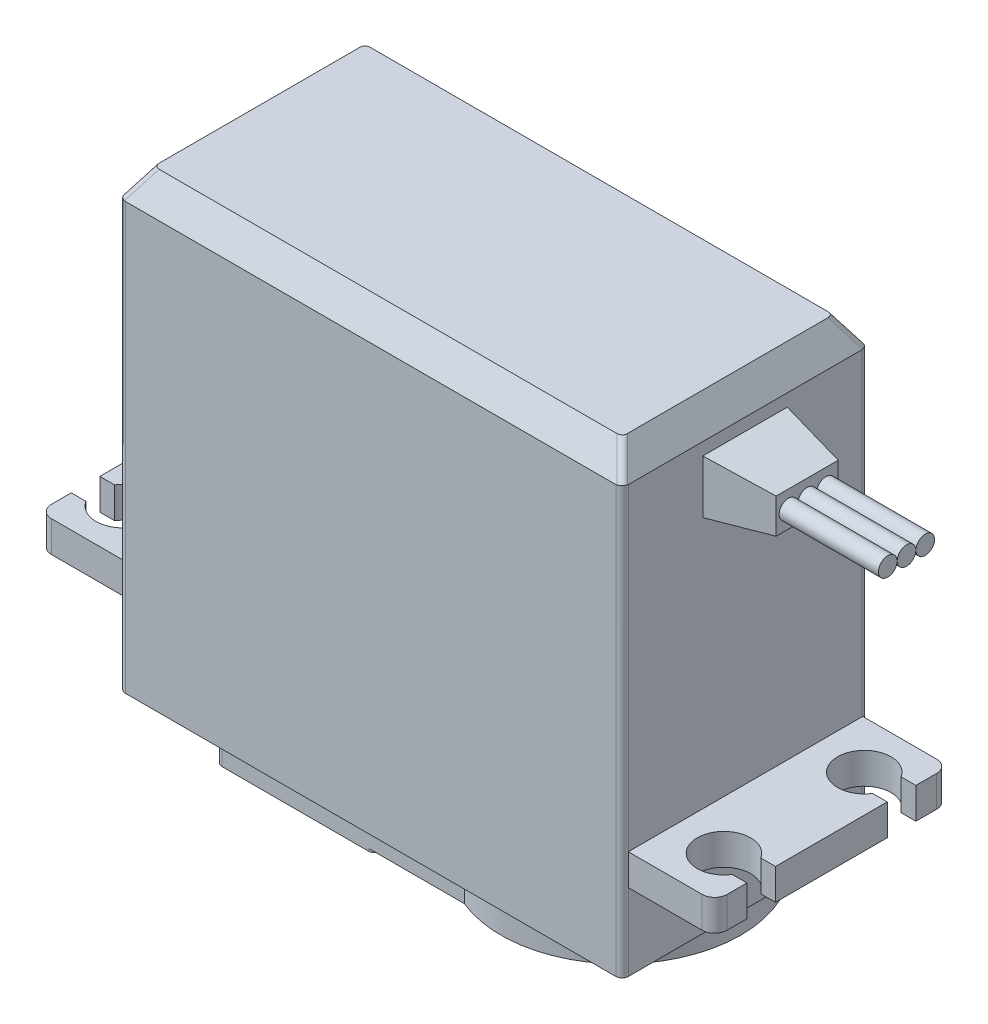
SolidWorks part; units mm, degrees
ref_plane "Front" through (0, 0, 0) normal (0, 0, 1) x (1, 0, 0)
ref_plane "Top" through (0, 0, 0) normal (0, 1, 0) x (1, 0, 0)
ref_plane "Right" through (0, 0, 0) normal (1, 0, 0) x (0, 0, -1)
sketch "Эскиз1" plane through (0, 0, 0) normal (0, 1, 0) x (1, 0, 0)
  line L1 (20.25, -9.9) -> (-20.25, -9.9)
  line L2 (20.25, -9.9) -> (20.25, 9.9)
  line L3 (20.25, 9.9) -> (-20.25, 9.9)
  line L4 (-20.25, -9.9) -> (-20.25, 9.9)
  line L5 (0, 9.9) -> (0, -9.9) construction
  line L6 (20.25, 0) -> (-20.25, 0) construction
  point P0 (0, 0)
  dimension "D1" = 19.8
  dimension "D2" = 40.5
extrude "Body" add sketch "Эскиз1" along normal blind 36.5
chamfer "Фаска1" distance 2.2 distance2 1.4 4 edges at (-20.25, 36.5, 0) (0, 36.5, -9.9) (20.25, 36.5, 0) (0, 36.5, 9.9) first distance on face at (-20.25, 18.25, 0) first distance on face at (0, 18.25, -9.9) first distance on face at (20.25, 18.25, 0) first distance on face at (0, 18.25, 9.9)
fillet "Скругление1" radius 0.5 8 edges at (-20.25, 17.15, -9.9) (-19.55, 35.4, -9.2) (19.55, 35.4, -9.2) (20.25, 17.15, -9.9) (19.55, 35.4, 9.2) (-19.55, 35.4, 9.2) (20.25, 17.15, 9.9) (-20.25, 17.15, 9.9)
ref_plane "Плоскость1" through (0, 6.2, 0) normal (0, -1, 0) x (-1, 0, 0)
sketch "Эскиз2" plane through (0, 6.2, 0) normal (0, -1, 0) x (-1, 0, 0)
  line L0 (-19.75, 9.9) -> (19.75, 9.9) construction
  line L1 (-26.2, 9.4728) -> (26.2, 9.4728)
  line L2 (27.2, -8.4) -> (27.2, -6.8)
  line L3 (-26.2, -9.4) -> (26.2, -9.4)
  line L4 (-27.2, -8.4) -> (-27.2, -6.8)
  line L5 (0, 9.9) -> (0, -9.9) construction
  line L6 (27.2, 0) -> (-27.2, 0) construction
  line L7 (-24.2, 5.65) -> (-27.2, 5.65) construction
  line L8 (-26.0166, 6.8) -> (-27.2, 6.8)
  line L9 (-26.0166, 4.5) -> (-27.2, 4.5)
  line L10 (-27.2, 6.8) -> (-27.2, 8.4728)
  line L11 (-26.0166, -4.5) -> (-27.2, -4.5)
  line L12 (-26.0166, -6.8) -> (-27.2, -6.8)
  line L13 (26.0166, -6.8) -> (27.2, -6.8)
  line L14 (26.0166, -4.5) -> (27.2, -4.5)
  line L15 (26.0166, 4.5) -> (27.2, 4.5)
  line L16 (26.0166, 6.8) -> (27.2, 6.8)
  line L17 (27.2, 6.8) -> (27.2, 8.4728)
  line L18 (27.2, -4.5) -> (27.2, 4.5)
  line L19 (-27.2, -4.5) -> (-27.2, 4.5)
  arc A0 (27.2, -8.4) -> (26.2, -9.4) centre (26.2, -8.4) cw
  arc A1 (26.2, 9.4728) -> (27.2, 8.4728) centre (26.2, 8.4728) cw
  arc A2 (-27.2, -8.4) -> (-26.2, -9.4) centre (-26.2, -8.4) ccw
  arc A3 (-27.2, 8.4728) -> (-26.2, 9.4728) centre (-26.2, 8.4728) cw
  arc A4 (-26.0166, 4.5) -> (-26.0166, 6.8) centre (-24.2, 5.65) ccw
  arc A5 (-26.0166, -4.5) -> (-26.0166, -6.8) centre (-24.2, -5.65) cw
  arc A6 (26.0166, -4.5) -> (26.0166, -6.8) centre (24.2, -5.65) ccw
  arc A7 (26.0166, 4.5) -> (26.0166, 6.8) centre (24.2, 5.65) cw
  point P0 (0, 0)
  point P10 (27.2, 9.9)
  point P16 (-27.2, 9.9)
  dimension "D2" = 1
  dimension "D4" = 4.3
  dimension "D1" = 54.4
  dimension "D5" = 3
  dimension "D6" = 1.15
extrude "Mount" add sketch "Эскиз2" against normal blind 2.5 contours L15 A7 L16 L17 A1 L1 A3 L10 L8 A4 L9 L4 L11 A5 L12 A2 L3 A0 L2 L13 A6 L14 L18 region at (0, 6.2, -0.039)
sketch "Эскиз3" plane through (0, 0, 0) normal (0, 0, 1) x (1, 0, 0)
  line L0 (-27.2, 6.2) -> (-20.25, 6.2)
  line L1 (-20.25, 6.2) -> (-20.25, 5.2)
  line L2 (-20.25, 0) -> (-20.25, 6.2) construction
  line L3 (-20.25, 5.2) -> (-27.2, 6.2)
  line L4 (0, 0) -> (0, 36.5) construction
  line L5 (-18.4282, 36.5) -> (18.4282, 36.5) construction
  line L6 (20.25, 5.2) -> (27.2, 6.2)
  line L7 (20.25, 6.2) -> (20.25, 5.2)
  line L8 (27.2, 6.2) -> (20.25, 6.2)
  dimension "D1" = 1
extrude "Бобышка-Вытянуть3" add sketch "Эскиз3" along normal mid plane 1
sketch "Эскиз4" plane through (0, 0, 0) normal (0, -1, 0) x (1, 0, 0)
  line L0 (20.25, 9.4) -> (20.25, -9.4) construction
  line L1 (-13.4526, -8.92) -> (-13.4526, -4.6)
  line L2 (-13.4526, -8.92) -> (6.5681, -8.92)
  line L3 (-13.4526, 8.92) -> (6.5681, 8.92)
  line L4 (-20.25, 0.5) -> (-20.25, -0.5) construction
  line L6 (-13.4526, 4.6) -> (-13.4526, 8.92)
  arc A0 (6.5681, -8.92) -> (6.5681, 8.92) centre (10.25, 0) ccw
  arc A1 (-13.4526, 4.6) -> (-13.4526, -4.6) centre (-11.493, 0) ccw
  point P2 (20.25, 0)
  point P6 (3.35, 0)
  dimension "D1" = 19.3
  dimension "D5" = 5
  dimension "D2" = 10
  dimension "D3" = 17.84
  dimension "D4" = 9.2
extrude "Бобышка-Вытянуть4" add sketch "Эскиз4" along normal blind 2
sketch "Эскиз5" plane through (0, -2, 0) normal (0, -1, 0) x (1, 0, 0)
  line L0 (-13.4526, -8.92) -> (6.5681, -8.92) construction
  line L1 (-13.4526, 8.92) -> (-0.6526, 8.92)
  line L2 (-13.4526, 8.92) -> (-13.4526, -8.92)
  line L3 (-13.4526, -8.92) -> (-0.6526, -8.92)
  line L4 (-0.6526, 8.92) -> (-0.6526, 2)
  line L5 (-0.6526, -2) -> (-0.6526, -8.92)
  line L7 (-1.6526, -7.92) -> (-12.4526, -7.92)
  line L8 (-1.6526, -7.92) -> (-1.6526, 7.92)
  line L9 (-1.6526, 7.92) -> (-12.4526, 7.92)
  line L10 (-12.4526, -7.92) -> (-12.4526, 7.92)
  line L11 (-7.0526, 7.92) -> (-7.0526, -7.92) construction
  line L12 (-1.6526, 0) -> (-12.4526, 0) construction
  arc A0 (-0.6526, 2) -> (-0.6526, -2) centre (-0.6526, 0) cw
  point P10 (-7.0526, 0)
  dimension "D2" = 2
  dimension "D1" = 12.8
  dimension "D3" = 1
  dimension "D4" = 15.84
  dimension "D5" = 10.8
extrude "Бобышка-Вытянуть5" add sketch "Эскиз5" along normal blind 0.2
sketch "Эскиз6" plane through (0, -2, 0) normal (0, -1, 0) x (1, 0, 0)
  circle A0 centre (10.25, 0) radius 6.6
  dimension "D1" = 13.2
extrude "Бобышка-Вытянуть6" add sketch "Эскиз6" along normal blind 1.2
sketch "Эскиз7" plane through (0, -3.2, 0) normal (0, -1, 0) x (1, 0, 0)
  circle A0 centre (10.25, 0) radius 5.35
  dimension "D1" = 10.7
extrude "Бобышка-Вытянуть7" add sketch "Эскиз7" along normal blind 0.5
sketch "Эскиз8" plane through (0, -3.7, 0) normal (0, -1, 0) x (1, 0, 0)
  circle A0 centre (10.25, 0) radius 2.6
  dimension "D1" = 5.2
extrude "Shaft hole" cut sketch "Эскиз8" against normal blind 10
fillet "Скругление2" radius 0.5 10 edges at (-13.4526, -1.1, 8.92) (-0.6526, -2.1, 2) (-0.6526, -2.1, -2) (-13.4526, -1.1, -8.92) (-1.6526, -2.1, 7.92) (-1.6526, -2.1, -7.92) (-12.4526, -2.1, 7.92) (-12.4526, -2.1, -7.92)
sketch "Эскиз9" plane through (20.25, 0, 0) normal (1, 0, 0) x (0, 0, -1)
  line L0 (-8.0782, 36.5) -> (8.0782, 36.5) construction
  line L1 (-3.4, 33.3) -> (3.4, 33.3)
  line L2 (-3.4, 33.3) -> (-3.4, 29)
  line L3 (-3.4, 29) -> (3.4, 29)
  line L4 (3.4, 33.3) -> (3.4, 29)
  line L5 (0, 29) -> (0, 33.3) construction
  line L6 (-3.4, 31.15) -> (3.4, 31.15) construction
  point P0 (0, 31.15)
  dimension "D1" = 3.2
  dimension "D2" = 6.8
  dimension "D3" = 4.3
ref_plane "Плоскость2" through (25.25, 0, 0) normal (1, 0, 0) x (0, 0, -1)
sketch "Эскиз10" plane through (25.25, 0, 0) normal (1, 0, 0) x (0, 0, -1)
  line L1 (-2.5, 29.75) -> (2.5, 29.75)
  line L2 (-2.5, 29.75) -> (-2.5, 32.55)
  line L3 (-2.5, 32.55) -> (2.5, 32.55)
  line L4 (2.5, 29.75) -> (2.5, 32.55)
  line L5 (0, 32.55) -> (0, 29.75) construction
  line L6 (-2.5, 31.15) -> (2.5, 31.15) construction
  point P0 (0, 31.15)
  dimension "D1" = 2.8
  dimension "D2" = 5
loft "Rubber" add profiles "Эскиз10", "Эскиз9" connector at (25.25, 32.55, 2.5) connector at (20.25, 33.3, 3.4)
sketch "Эскиз11" plane through (25.25, 0, 0) normal (1, 0, 0) x (0, 0, -1)
  circle A0 centre (0, 31.1505) radius 0.75
  circle A1 centre (1.51, 31.15) radius 0.75
  circle A2 centre (-1.51, 31.15) radius 0.75
  dimension "D1" = 1.5
  dimension "D2" = 1.51
  dimension "D3" = 1.51
extrude "Бобышка-Вытянуть10" add sketch "Эскиз11" along normal blind 8
